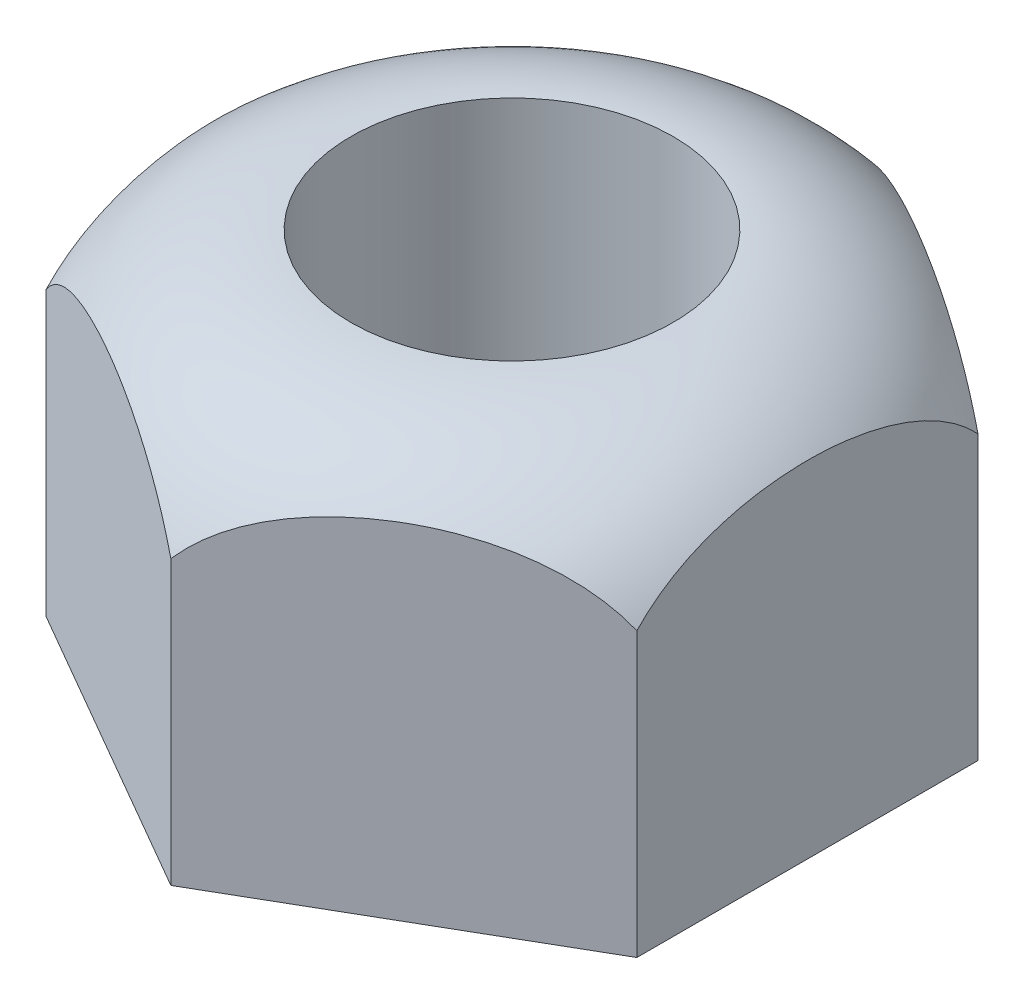
SolidWorks part; units mm, degrees
ref_plane "Front Plane" through (0, 0, 0) normal (0, 0, 1) x (1, 0, 0)
ref_plane "Top Plane" through (0, 0, 0) normal (0, 1, 0) x (1, 0, 0)
ref_plane "Right Plane" through (0, 0, 0) normal (1, 0, 0) x (0, 0, -1)
sketch "Sketch1" plane through (0, 0, 0) normal (0, 1, 0) x (1, 0, 0)
  line L0 (0, 1.5) -> (0, 1) construction
  line L1 (0, 3.1754) -> (-2.75, 1.5877) construction
  line L2 (-2.75, 1.5877) -> (-2.75, -1.5877) construction
  line L3 (-2.75, -1.5877) -> (0, -3.1754) construction
  line L4 (0, -3.1754) -> (2.75, -1.5877) construction
  line L5 (2.75, -1.5877) -> (2.75, 1.5877) construction
  line L6 (2.75, 1.5877) -> (0, 3.1754) construction
  circle A0 centre (0, 0) radius 2.75 construction
  circle A1 centre (0, 0) radius 1.5 construction
  point P12 (0, -1.5)
  dimension "Thread Size" = 3
  dimension "Width" = 5.5
  dimension "Thread Pitch" = 0.5
sketch "Sketch2" plane through (0, 0, 0) normal (0, 0, 1) x (1, 0, 0)
  line L0 (0, -1.85) -> (0, 1.85) construction
  point P4 (0, 0)
  dimension "Height" = 3.7
sketch "Sketch3" plane through (0, 0, 0) normal (0, 1, 0) x (1, 0, 0)
  line L0 (2.75, 1.5877) -> (0, 3.1754) construction
  line L1 (2.75, -1.5877) -> (2.75, 1.5877) construction
  line L2 (0, -3.1754) -> (2.75, -1.5877) construction
  line L3 (-2.75, -1.5877) -> (0, -3.1754) construction
  line L4 (-2.75, 1.5877) -> (-2.75, -1.5877) construction
  line L5 (0, 3.1754) -> (-2.75, 1.5877) construction
  line L6 (2.75, 1.5877) -> (0, 3.1754)
  line L7 (2.75, -1.5877) -> (2.75, 1.5877)
  line L8 (0, -3.1754) -> (2.75, -1.5877)
  line L9 (-2.75, -1.5877) -> (0, -3.1754)
  line L10 (-2.75, 1.5877) -> (-2.75, -1.5877)
  line L11 (0, 3.1754) -> (-2.75, 1.5877)
  circle A0 centre (0, 0) radius 1.5 construction
  circle A1 centre (0, 0) radius 1.5
extrude "Boss-Extrude1" add sketch "Sketch3" along normal mid plane 3.7
ref_plane "Plane1" through (0, 1.85, 0) normal (0, 1, 0) x (1, 0, 0)
sketch "Sketch5" plane through (0, 0, 0) normal (1, 0, 0) x (0, 0, -1)
  line L0 (3.1754, 1.85) -> (3.1754, -1.85) construction
  line L1 (1.5877, 1.85) -> (3.1754, 1.85) construction
  line L3 (1.5, 1.85) -> (3.1754, 1.85)
  line L4 (3.1754, 1.85) -> (3.1754, 0.7845)
  line L5 (0, 0) -> (0, 1.85) construction
  line L6 (0, -1.85) -> (0, 1.85) construction
  arc A0 (1.5, 1.85) -> (3.1754, 0.7845) centre (1.5, 0) cw
  dimension "D1" = 1.85
revolve "Cut-Revolve1" cut sketch "Sketch5" angle 360 about L5
sketch "Ref" plane through (0, 0, 0) normal (0, 0, 1) x (1, 0, 0)
  line L0 (-2.75, -1.85) -> (-2.75, 1.85) construction
  dimension "D1" = 3.7
sketch "Sketch7" [suppressed] plane through (0, 1.85, 0) normal (0, 1, 0) x (1, 0, 0)
  circle A0 centre (0, 0) radius 1.5 construction
  circle A1 centre (0, 0) radius 1.5
curve "Helix/Spiral1" [suppressed] pitch 0.5 height 4.2 turns 8.4
sketch "Sketch8" [suppressed] plane through (0, 0, 0) normal (0, 0, 1) x (1, 0, 0)
  line L0 (-1.5, 2.2875) -> (-1.5, 1.85)
  line L1 (-1.5, 1.85) -> (-1.1752, 2.0375)
  line L2 (-1.1752, 2.1) -> (-1.5, 2.2875)
  line L3 (-1.1752, 2.1) -> (-1.1752, 2.0375)
  line L4 (-1.1752, 2.0688) -> (-1.5, 2.0688) construction
  line L5 (-1.3376, 1.9438) -> (-1.3376, 2.1938) construction
  point P11 (-1.3376, 2.0688)
  dimension "D1" = 60
  dimension "D2" = 0.0625
  dimension "D3" = 0.25
sweep "Sweep1" [suppressed] add profiles "Sketch8" path "Helix/Spiral1"
sketch "Sketch9" [suppressed] plane through (0, 1.85, 0) normal (0, 1, 0) x (1, 0, 0)
  circle A1 centre (0, 0) radius 1.5
  circle A2 centre (0, 0) radius 1.5
  dimension "D1" = 0
extrude "Cut-Extrude2" [suppressed] cut sketch "Sketch9" along normal through all
mirror "Mirror1" [suppressed] about plane through (0, 0, 0) normal (0, 1, 0)
sketch "Sketch10" [suppressed] plane through (0, 1.85, 0) normal (0, 1, 0) x (1, 0, 0)
  circle A0 centre (0, 0) radius 1.55
  circle A2 centre (0, 0) radius 1.5 construction
  dimension "D2" = 3
  dimension "D1" = 0.05
extrude "Cut-Extrude3" [suppressed] cut sketch "Sketch10" against normal through all draft 45
equation "\"D1@Boss-Extrude1\"=\"Height@Sketch2\""
equation "\"D1@Sketch5\"=(\"Height@Sketch2\"*.5)"
equation "\"D4@Helix/Spiral1\"=\"Thread Pitch@Sketch1\""
equation "\"D3@Helix/Spiral1\"=\"Height@Sketch2\"+\"Thread Pitch@Sketch1\""
equation "\"D2@Sketch8\"=\"Thread Pitch@Sketch1\"*.125"
equation "\"D3@Sketch8\"=\"Thread Pitch@Sketch1\"*.5"
equation "\"D3@Cut-Extrude3\"=\"Thread Pitch@Sketch1\"*.75"
equation "\"D1@Sketch10\"=\"Thread Pitch@Sketch1\"*.1"
equation "\"D2@Sketch10\"=\"Thread Size@Sketch1\""
equation "\"D1@Ref\"=\"Height@Sketch2\""
